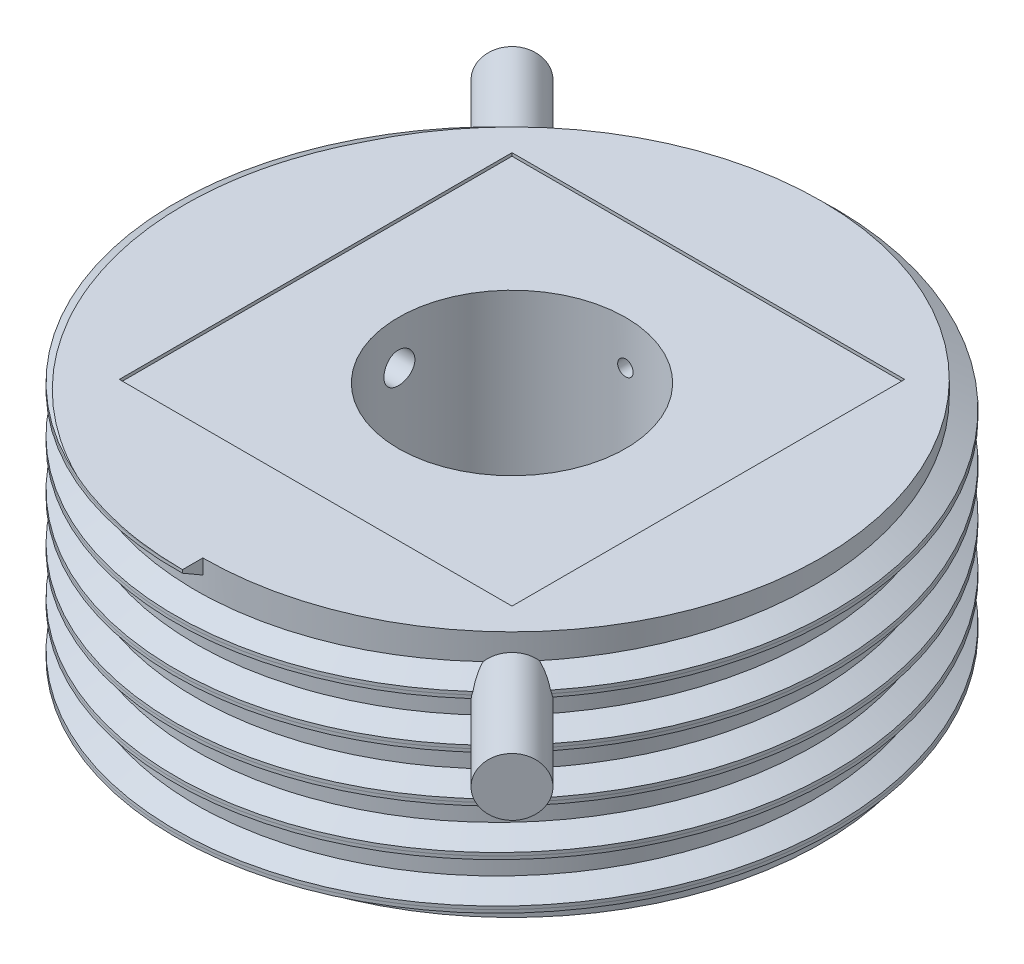
SolidWorks part; units mm, degrees
ref_plane "Front Plane" through (0, 0, 0) normal (0, 0, 1) x (1, 0, 0)
ref_plane "Top Plane" through (0, 0, 0) normal (0, 1, 0) x (1, 0, 0)
ref_plane "Right Plane" through (0, 0, 0) normal (1, 0, 0) x (0, 0, -1)
sketch "innerCircle" plane through (0, 0, 0) normal (0, 1, 0) x (1, 0, 0)
  circle A0 centre (0, 0) radius 7.35
  circle A1 centre (0, 0) radius 20
  dimension "D1" = 14.7
  dimension "D2" = 40
extrude "Circle" add sketch "innerCircle" along normal blind 16
sketch "Sketch5" plane through (0, 16, 0) normal (0, 1, 0) x (1, 0, 0)
  line L1 (12.7, 12.7) -> (-12.7, 12.7)
  line L2 (12.7, 12.7) -> (12.7, -12.7)
  line L3 (12.7, -12.7) -> (-12.7, -12.7)
  line L4 (-12.7, 12.7) -> (-12.7, -12.7)
  line L5 (12.7, 12.7) -> (-12.7, -12.7) construction
  line L6 (12.7, -12.7) -> (-12.7, 12.7) construction
  point P0 (0, 0)
  dimension "D1" = 25.4
  dimension "D2" = 25.4
sketch "Sketch11" plane through (0, 0, 0) normal (0, 0, 1) x (1, 0, 0)
  line L0 (0, 16) -> (0, 0) construction
  point P5 (0, 0)
  point P6 (0, 0)
ref_plane "Plane1" through (0, 16, 0) normal (0, 1, 0) x (1, 0, 0)
sketch "Sketch13" plane through (0, 16, 0) normal (0, 1, 0) x (1, 0, 0)
  circle A0 centre (0, 0) radius 20
curve "Helix/Spiral1" pitch 3 height 16 radius 20 centre (0, 16, 0) axis (0, -1, 0) start towards (0, 0, 1)
sketch "Sketch14" plane through (0, 0, 0) normal (1, 0, 0) x (0, 0, -1)
  line L0 (-19.8126, 16) -> (-21.3126, 16) construction
  line L1 (20, 16) -> (-20, 16) construction
  line L2 (-21.3126, 16) -> (-21.3126, 16.2)
  line L3 (-21.3126, 16.2) -> (-19.8126, 17.066)
  line L4 (-19.8126, 17.066) -> (-19.8126, 14.934)
  line L5 (-19.8126, 14.934) -> (-21.3126, 15.8)
  line L6 (-21.3126, 15.8) -> (-21.3126, 16)
  dimension "D1" = 1.5
  dimension "D2" = 60
  dimension "D3" = 0.2
sweep "Sweep1" add profiles "Sketch14" path "Helix/Spiral1"
sketch "Sketch15" plane through (0, 0, 0) normal (1, 0, 0) x (0, 0, -1)
  line L0 (0, 16) -> (0, 0) construction
  circle A0 centre (0, 12.9718) radius 1
  dimension "D1" = 2
sketch "Sketch16" plane through (0, 0, 0) normal (0, 0, 1) x (1, 0, 0)
  line L0 (0, 11.9718) -> (0, 13.9718) construction
  circle A0 centre (0, 12.9718) radius 0.5
  dimension "D1" = 1
extrude "Cut-Extrude2" cut sketch "Sketch16" against normal through all
extrude "Cut-Extrude3" cut sketch "Sketch15" against normal through all
ref_plane "Plane2" through (0, 0, 0) normal (0.7071, 0, 0.7071) x (0, -1, 0)
sketch "Sketch17" plane through (0, 0, 0) normal (0.7071, 0, 0.7071) x (0, -1, 0)
  circle A0 centre (-12.9718, 0) radius 1.875
  dimension "D1" = 3.75
extrude "Boss-Extrude1" add sketch "Sketch17" along normal blind 28 and the other way blind 28
sketch "Sketch18" plane through (0, 0, 0) normal (0, 1, 0) x (1, 0, 0)
  circle A0 centre (0, 0) radius 7.35
  dimension "D1" = 14.7
extrude "Cut-Extrude4" cut sketch "Sketch18" along normal through all
sketch "Sketch19" plane through (0, 0, 0) normal (1, 0, 0) x (0, 0, -1)
  line L0 (25, -2) -> (-25, -2) construction
  line L1 (-19.9189, 0) -> (20.6045, 0)
  line L2 (-19.9189, 0) -> (-19.9189, -2)
  line L3 (-19.9189, -2) -> (20.6045, -2)
  line L4 (20.6045, 0) -> (20.6045, -2)
  spline S0 degree 2 poles (-15.3428, 12.3739) (-15.7799, 12.3579) (-16.1803, 12.3422) (-20, 12.1922) (-20, 12.0422) (-20, 11.8922) (-16.1803, 11.7422) (-12.3607, 11.5922) (-6.1803, 11.4422) (0, 11.2922) (6.1803, 11.1422) (12.3607, 10.9922) (16.1803, 10.8422) (20, 10.6922) (20, 10.5422) (20, 10.3922) (16.1803, 10.2422) (12.3607, 10.0922) (6.1803, 9.9422) (0, 9.7922) (-6.1803, 9.6422) (-12.3607, 9.4922) (-16.1803, 9.3422) (-20, 9.1922) (-20, 9.0422) (-20, 8.8922) (-16.1803, 8.7422) (-12.3607, 8.5922) (-6.1803, 8.4422) (0, 8.2922) (6.1803, 8.1422) (12.3607, 7.9922) (16.1803, 7.8422) (20, 7.6922) (20, 7.5422) (20, 7.3922) (16.1803, 7.2422) (12.3607, 7.0922) (6.1803, 6.9422) (0, 6.7922) (-6.1803, 6.6422) (-12.3607, 6.4922) (-16.1803, 6.3422) (-20, 6.1922) (-20, 6.0422) (-20, 5.8922) (-16.1803, 5.7422) (-12.3607, 5.5922) (-6.1803, 5.4422) (0, 5.2922) (6.1803, 5.1422) (12.3607, 4.9922) (16.1803, 4.8422) (20, 4.6922) (20, 4.5422) (20, 4.3922) (16.1803, 4.2422) (12.3607, 4.0922) (6.1803, 3.9422) (0, 3.7922) (-6.1803, 3.6422) (-12.3607, 3.4922) (-16.1803, 3.3422) (-20, 3.1922) (-20, 3.0422) (-20, 2.8922) (-16.1803, 2.7422) (-12.3607, 2.5922) (-6.1803, 2.4422) (0, 2.2922) (6.1803, 2.1422) (12.3607, 1.9922) (16.1803, 1.8422) (20, 1.6922) (20, 1.5422) (20, 1.3922) (16.1803, 1.2422) (12.3607, 1.0922) (6.1803, 0.9422) (0, 0.7922) (-6.1803, 0.6422) (-12.3607, 0.4922) (-16.1803, 0.3422) (-20, 0.1922) (-20, 0.0422) (-20, 0.0213) (-19.9189, 0) knots 0.148172 0.148172 0.148172 0.15 0.15 0.166667 0.166667 0.183333 0.183333 0.2 0.2 0.216667 0.216667 0.233333 0.233333 0.25 0.25 0.266667 0.266667 0.283333 0.283333 0.3 0.3 0.316667 0.316667 0.333333 0.333333 0.35 0.35 0.366667 0.366667 0.383333 0.383333 0.4 0.4 0.416667 0.416667 0.433333 0.433333 0.45 0.45 0.466667 0.466667 0.483333 0.483333 0.5 0.5 0.516667 0.516667 0.533333 0.533333 0.55 0.55 0.566667 0.566667 0.583333 0.583333 0.6 0.6 0.616667 0.616667 0.633333 0.633333 0.65 0.65 0.666667 0.666667 0.683333 0.683333 0.7 0.7 0.716667 0.716667 0.733333 0.733333 0.75 0.75 0.766667 0.766667 0.783333 0.783333 0.8 0.8 0.816667 0.816667 0.833333 0.833333 0.835748 0.835748 0.835748 weights 0.990444 0.994633 1 0.951057 1 0.951057 1 0.951057 1 0.951057 1 0.951057 1 0.951057 1 0.951057 1 0.951057 1 0.951057 1 0.951057 1 0.951057 1 0.951057 1 0.951057 1 0.951057 1 0.951057 1 0.951057 1 0.951057 1 0.951057 1 0.951057 1 0.951057 1 0.951057 1 0.951057 1 0.951057 1 0.951057 1 0.951057 1 0.951057 1 0.951057 1 0.951057 1 0.951057 1 0.951057 1 0.951057 1 0.951057 1 0.951057 1 0.951057 1 0.951057 1 0.951057 1 0.951057 1 0.951057 1 0.951057 1 0.951057 1 0.951057 1 0.99291 0.987874 construction
  dimension "D1" = 40.5234
  dimension "D2" = 2
extrude "Cut-Extrude5" cut sketch "Sketch19" against normal through all both and the other way through all
sketch "Sketch20" plane through (0, 0, 0) normal (1, 0, 0) x (0, 0, -1)
  line L1 (20, 16) -> (-21.3126, 16)
  line L2 (20, 16) -> (20, 18.2403)
  line L3 (20, 18.2403) -> (-21.3126, 18.2403)
  line L4 (-21.3126, 16) -> (-21.3126, 18.2403)
  dimension "D1" = 41.3126
  dimension "D2" = 2.2403
extrude "Cut-Extrude6" cut sketch "Sketch20" against normal through all both and the other way through all
sketch "Sketch21" plane through (0, 0, 0) normal (0, -1, 0) x (1, 0, 0)
  circle A0 centre (0, 0) radius 14
  circle A1 centre (0, 0) radius 12.3
  dimension "D1" = 28
  dimension "D2" = 1.7
extrude "Cut-Extrude7" cut sketch "Sketch21" against normal blind 0.7
sketch "Sketch22" plane through (0, 16, 0) normal (0, 1, 0) x (1, 0, 0)
  line L1 (-12.7, -12.7) -> (12.7, -12.7)
  line L2 (-12.7, -12.7) -> (-12.7, 12.7)
  line L3 (-12.7, 12.7) -> (12.7, 12.7)
  line L4 (12.7, -12.7) -> (12.7, 12.7)
  line L5 (-12.7, -12.7) -> (12.7, 12.7) construction
  line L6 (-12.7, 12.7) -> (12.7, -12.7) construction
  point P0 (0, 0)
extrude "Cut-Extrude8" cut sketch "Sketch22" against normal blind 0.2
equation "\"1inch\"=30"
